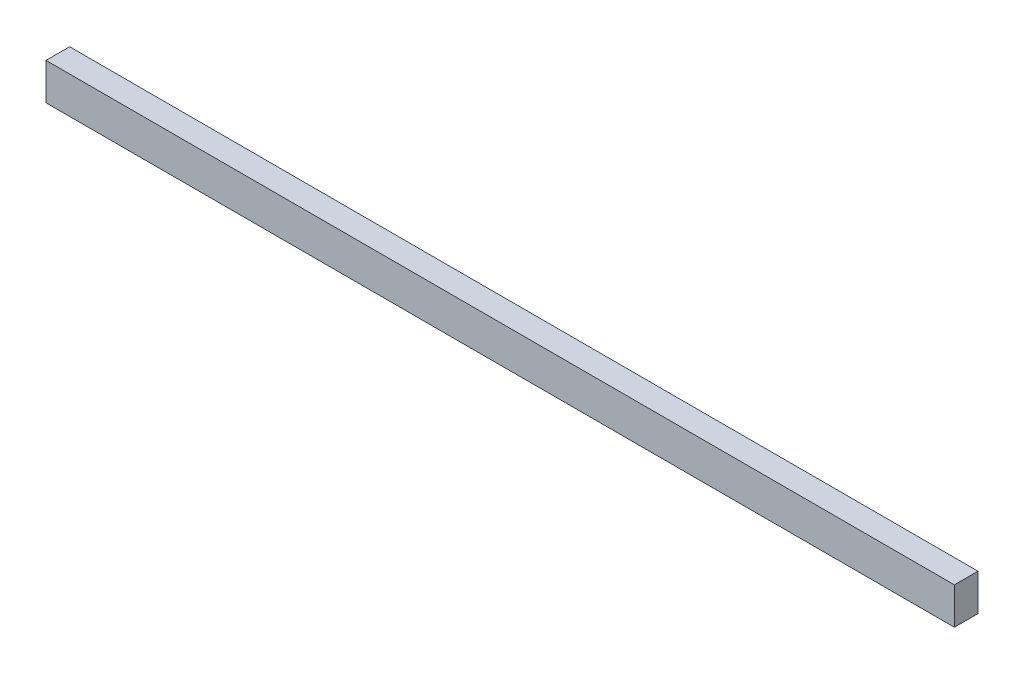
SolidWorks part; units mm, degrees
material "Pine"
ref_plane "Front Plane" through (0, 0, 0) normal (0, 0, 1) x (1, 0, 0)
ref_plane "Top Plane" through (0, 0, 0) normal (0, 1, 0) x (1, 0, 0)
ref_plane "Right Plane" through (0, 0, 0) normal (1, 0, 0) x (0, 0, -1)
sketch "Sketch1" plane through (0, 0, 0) normal (1, 0, 0) x (0, 0, -1)
  line L1 (0, 0) -> (45, 0)
  line L2 (0, 0) -> (0, 70)
  line L3 (0, 70) -> (45, 70)
  line L4 (45, 0) -> (45, 70)
  dimension "D1" = 70
  dimension "D2" = 45
extrude "Boss-Extrude1" add sketch "Sketch1" along normal blind 1730
